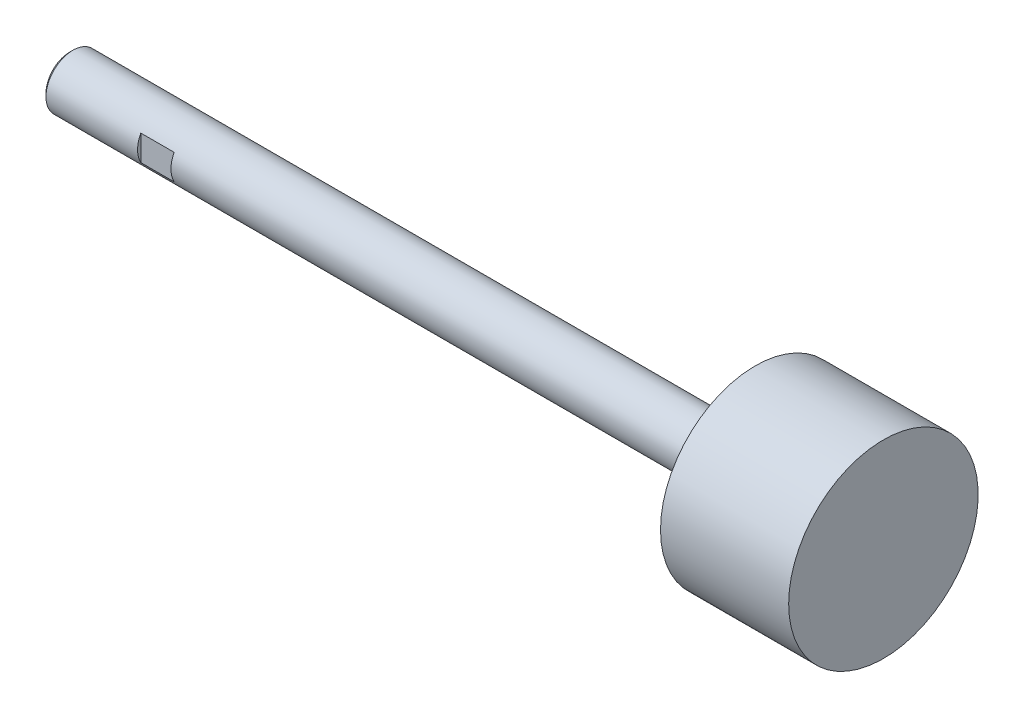
SolidWorks part; units mm, degrees
material "Cast Alloy Steel"
ref_plane "Front Plane" through (0, 0, 0) normal (0, 0, 1) x (1, 0, 0)
ref_plane "Top Plane" through (0, 0, 0) normal (0, 1, 0) x (1, 0, 0)
ref_plane "Right Plane" through (0, 0, 0) normal (1, 0, 0) x (0, 0, -1)
sketch "Sketch1" plane through (0, 0, 0) normal (0, 0, 1) x (1, 0, 0)
  line L0 (-7.874, 0) -> (-7.874, 6.35)
  line L1 (-7.874, 6.35) -> (131.445, 6.35)
  line L2 (131.445, 6.35) -> (131.445, 22.3456)
  line L3 (131.445, 22.3456) -> (161.671, 22.3456)
  line L4 (161.671, 22.3456) -> (161.671, 0)
  line L5 (161.671, 0) -> (-7.874, 0)
  line L6 (161.671, 0) -> (-7.874, 0) construction
revolve "Revolve1" add sketch "Sketch1" angle 360 about L6 reverse direction yes
cosmetic thread "Cosmetic Thread1" parameters "D1"=22.352, "D2"=11.1887
sketch "Sketch2" plane through (0, 0, 0) normal (0, 0, 1) x (1, 0, 0)
  line L0 (-30.226, 0) -> (-30.226, 5.5944)
  line L1 (-30.226, 5.5944) -> (-29.4703, 6.35)
  line L2 (-29.4703, 6.35) -> (-7.874, 6.35)
  line L3 (-7.874, 6.35) -> (-7.874, 0)
  line L4 (-7.874, 0) -> (-30.226, 0)
  line L5 (-7.874, 0) -> (-30.226, 0) construction
revolve "Revolve2" add sketch "Sketch2" angle 360 about L5 reverse direction yes
ref_plane "Plane1" through (0, 0, 0) normal (1, 0, 0) x (0, 0, -1)
ref_plane "Plane2" through (-7.874, 0, 0) normal (1, 0, 0) x (0, 0, -1)
sketch "Sketch3" plane through (-7.874, 0, 0) normal (1, 0, 0) x (0, 0, -1)
  line L0 (-12.7, 12.7) -> (-12.7, -12.7)
  line L1 (-12.7, -12.7) -> (12.7, -12.7)
  line L2 (12.7, -12.7) -> (12.7, 12.7)
  line L3 (12.7, 12.7) -> (-12.7, 12.7)
  line L4 (-5.588, 6.35) -> (-5.588, -6.35)
  line L5 (-5.588, -6.35) -> (5.588, -6.35)
  line L6 (5.588, -6.35) -> (5.588, 6.35)
  line L7 (5.588, 6.35) -> (-5.588, 6.35)
extrude "Cut-Extrude1" cut sketch "Sketch3" along normal blind 7.874
ref_plane "Plane3" through (300.99, 0, 0) normal (1, 0, 0) x (0, 0, -1)
ref_plane "Plane4" through (-30.226, 0, 0) normal (1, 0, 0) x (0, 0, -1)
ref_plane "Plane5" through (-7.874, 0, 0) normal (1, 0, 0) x (0, 0, -1)
ref_plane "Plane6" through (0, 0, 0) normal (1, 0, 0) x (0, 0, -1)
ref_plane "Plane7" through (0, 0, 0) normal (0, 0, 1) x (1, 0, 0)
ref_plane "Plane8" through (0, 0, 0) normal (1, 0, 0) x (0, 0, -1)
ref_plane "Plane9" through (0, 0, 0) normal (0, 1, 0) x (1, 0, 0)
ref_plane "Plane10" through (-34.798, 0, 0) normal (1, 0, 0) x (0, 0, -1)
ref_plane "dia1 XY" through (-7.874, 0, 0) normal (1, 0, 0) x (0, 0, -1)
ref_plane "dia1 XZ" through (0, 6.35, 0) normal (0, -1, 0) x (-1, 0, 0)
ref_plane "dia1 YZ" through (0, 0, 0) normal (0, 0, -1) x (-1, 0, 0)
ref_axis "dia1 X" through (-7.874, 6.35, 80.9) along (0, 0, -1)
ref_axis "dia1 Y" through (-7.874, -50, 0) along (0, 1, 0)
ref_axis "dia1 Z" through (80.9, 6.35, 0) along (-1, 0, 0)
sketch3d "dia1"
  point P0 (-7.874, 6.35, 0)
ref_plane "dia12 XY" through (0, 0, 0) normal (1, 0, 0) x (0, 0, -1)
ref_plane "dia12 XZ" through (0, 0, 0) normal (0, -1, 0) x (-1, 0, 0)
ref_plane "dia12 YZ" through (0, 0, 23.4251) normal (0, 0, -1) x (-1, 0, 0)
ref_axis "dia12 X" through (0, 0, 80.9) along (0, 0, -1)
ref_axis "dia12 Y" through (0, -50, 23.4251) along (0, 1, 0)
ref_axis "dia12 Z" through (80.9, 0, 23.4251) along (-1, 0, 0)
sketch3d "dia12"
  point P0 (0, 0, 23.4251)
ref_plane "dia2 XY" through (-7.874, 0, 0) normal (1, 0, 0) x (0, 0, -1)
ref_plane "dia2 XZ" through (0, -6.35, 0) normal (0, -1, 0) x (-1, 0, 0)
ref_plane "dia2 YZ" through (0, 0, 0) normal (0, 0, -1) x (-1, 0, 0)
ref_axis "dia2 X" through (-7.874, -6.35, 80.9) along (0, 0, -1)
ref_axis "dia2 Y" through (-7.874, -50, 0) along (0, 1, 0)
ref_axis "dia2 Z" through (80.9, -6.35, 0) along (-1, 0, 0)
sketch3d "dia2"
  point P0 (-7.874, -6.35, 0)
ref_plane "dia22 XY" through (0, 0, 0) normal (1, 0, 0) x (0, 0, -1)
ref_plane "dia22 XZ" through (0, 0, 0) normal (0, -1, 0) x (-1, 0, 0)
ref_plane "dia22 YZ" through (0, 0, -23.4251) normal (0, 0, -1) x (-1, 0, 0)
ref_axis "dia22 X" through (0, 0, 80.9) along (0, 0, -1)
ref_axis "dia22 Y" through (0, -50, -23.4251) along (0, 1, 0)
ref_axis "dia22 Z" through (80.9, 0, -23.4251) along (-1, 0, 0)
sketch3d "dia22"
  point P0 (0, 0, -23.4251)
ref_plane "hh1 XY" through (0, 0, 0) normal (0, 0, 1) x (1, 0, 0)
ref_plane "hh1 XZ" through (0, 0, 0) normal (0, -1, 0) x (-1, 0, 0)
ref_plane "hh1 YZ" through (204.5081, 0, 0) normal (1, 0, 0) x (0, 0, -1)
ref_axis "hh1 X" through (-80.9, 0, 0) along (1, 0, 0)
ref_axis "hh1 Y" through (204.5081, -50, 0) along (0, 1, 0)
ref_axis "hh1 Z" through (204.5081, 0, 80.9) along (0, 0, -1)
sketch3d "hh1"
  point P0 (204.5081, 0, 0)
ref_plane "hh2 XY" through (0, 0, 0) normal (0, 0, 1) x (1, 0, 0)
ref_plane "hh2 XZ" through (0, 0, 0) normal (0, -1, 0) x (-1, 0, 0)
ref_plane "hh2 YZ" through (214.0839, 0, 0) normal (1, 0, 0) x (0, 0, -1)
ref_axis "hh2 X" through (-80.9, 0, 0) along (1, 0, 0)
ref_axis "hh2 Y" through (214.0839, -50, 0) along (0, 1, 0)
ref_axis "hh2 Z" through (214.0839, 0, 80.9) along (0, 0, -1)
sketch3d "hh2"
  point P0 (214.0839, 0, 0)
ref_plane "rl1 XY" through (-30.226, 0, 0) normal (1, 0, 0) x (0, 0, -1)
ref_plane "rl1 XZ" through (0, 0, 0) normal (0, -1, 0) x (-1, 0, 0)
ref_plane "rl1 YZ" through (0, 0, 0) normal (0, 0, -1) x (-1, 0, 0)
ref_axis "rl1 X" through (-30.226, 0, 80.9) along (0, 0, -1)
ref_axis "rl1 Y" through (-30.226, -50, 0) along (0, 1, 0)
ref_axis "rl1 Z" through (80.9, 0, 0) along (-1, 0, 0)
sketch3d "rl1"
  point P0 (-30.226, 0, 0)
ref_plane "rl2 XY" through (-7.874, 0, 0) normal (1, 0, 0) x (0, 0, -1)
ref_plane "rl2 XZ" through (0, 0, 0) normal (0, -1, 0) x (-1, 0, 0)
ref_plane "rl2 YZ" through (0, 0, 0) normal (0, 0, -1) x (-1, 0, 0)
ref_axis "rl2 X" through (-7.874, 0, 80.9) along (0, 0, -1)
ref_axis "rl2 Y" through (-7.874, -50, 0) along (0, 1, 0)
ref_axis "rl2 Z" through (80.9, 0, 0) along (-1, 0, 0)
sketch3d "rl2"
  point P0 (-7.874, 0, 0)
ref_plane "rod_cp XY" through (0, 0, 0) normal (1, 0, 0) x (0, 0, -1)
ref_plane "rod_cp XZ" through (0, 0, 0) normal (0, -1, 0) x (-1, 0, 0)
ref_plane "rod_cp YZ" through (0, 0, 0) normal (0, 0, -1) x (-1, 0, 0)
ref_axis "rod_cp X" through (0, 0, 80.9) along (0, 0, -1)
ref_axis "rod_cp Y" through (0, -50, 0) along (0, 1, 0)
ref_axis "rod_cp Z" through (80.9, 0, 0) along (-1, 0, 0)
sketch3d "rod_cp"
  point P0 (0, 0, 0)
ref_plane "thd1 XY" through (-30.226, 0, 0) normal (1, 0, 0) x (0, 0, -1)
ref_plane "thd1 XZ" through (0, 6.35, 0) normal (0, -1, 0) x (-1, 0, 0)
ref_plane "thd1 YZ" through (0, 0, 0) normal (0, 0, -1) x (-1, 0, 0)
ref_axis "thd1 X" through (-30.226, 6.35, 80.9) along (0, 0, -1)
ref_axis "thd1 Y" through (-30.226, -50, 0) along (0, 1, 0)
ref_axis "thd1 Z" through (80.9, 6.35, 0) along (-1, 0, 0)
sketch3d "thd1"
  point P0 (-30.226, 6.35, 0)
ref_plane "thd2 XY" through (-30.226, 0, 0) normal (1, 0, 0) x (0, 0, -1)
ref_plane "thd2 XZ" through (0, -6.35, 0) normal (0, -1, 0) x (-1, 0, 0)
ref_plane "thd2 YZ" through (0, 0, 0) normal (0, 0, -1) x (-1, 0, 0)
ref_axis "thd2 X" through (-30.226, -6.35, 80.9) along (0, 0, -1)
ref_axis "thd2 Y" through (-30.226, -50, 0) along (0, 1, 0)
ref_axis "thd2 Z" through (80.9, -6.35, 0) along (-1, 0, 0)
sketch3d "thd2"
  point P0 (-30.226, -6.35, 0)
ref_plane "to_rod_clevis XY" through (-34.798, 0, 0) normal (1, 0, 0) x (0, 0, -1)
ref_plane "to_rod_clevis XZ" through (0, 0, 0) normal (0, -1, 0) x (-1, 0, 0)
ref_plane "to_rod_clevis YZ" through (0, 0, 0) normal (0, 0, -1) x (-1, 0, 0)
ref_axis "to_rod_clevis X" through (-34.798, 0, 80.9) along (0, 0, -1)
ref_axis "to_rod_clevis Y" through (-34.798, -50, 0) along (0, 1, 0)
ref_axis "to_rod_clevis Z" through (80.9, 0, 0) along (-1, 0, 0)
sketch3d "to_rod_clevis"
  point P0 (-34.798, 0, 0)
ref_plane "wf1 XY" through (-7.874, 0, 0) normal (1, 0, 0) x (0, 0, -1)
ref_plane "wf1 XZ" through (0, 0, 0) normal (0, -1, 0) x (-1, 0, 0)
ref_plane "wf1 YZ" through (0, 0, 0) normal (0, 0, -1) x (-1, 0, 0)
ref_axis "wf1 X" through (-7.874, 0, 80.9) along (0, 0, -1)
ref_axis "wf1 Y" through (-7.874, -50, 0) along (0, 1, 0)
ref_axis "wf1 Z" through (80.9, 0, 0) along (-1, 0, 0)
sketch3d "wf1"
  point P0 (-7.874, 0, 0)
ref_plane "wf2 XY" through (0, 0, 0) normal (1, 0, 0) x (0, 0, -1)
ref_plane "wf2 XZ" through (0, 0, 0) normal (0, -1, 0) x (-1, 0, 0)
ref_plane "wf2 YZ" through (0, 0, 0) normal (0, 0, -1) x (-1, 0, 0)
ref_axis "wf2 X" through (0, 0, 80.9) along (0, 0, -1)
ref_axis "wf2 Y" through (0, -50, 0) along (0, 1, 0)
ref_axis "wf2 Z" through (80.9, 0, 0) along (-1, 0, 0)
sketch3d "wf2"
  point P0 (0, 0, 0)
ref_plane "wfw1 XY" through (0, 0, 0) normal (0, 1, 0) x (1, 0, 0)
ref_plane "wfw1 XZ" through (0, 0, -5.588) normal (0, 0, 1) x (1, 0, 0)
ref_plane "wfw1 YZ" through (-7.874, 0, 0) normal (1, 0, 0) x (0, 0, -1)
ref_axis "wfw1 X" through (-80.9, 0, -5.588) along (1, 0, 0)
ref_axis "wfw1 Y" through (-7.874, 0, 50) along (0, 0, -1)
ref_axis "wfw1 Z" through (-7.874, 50, -5.588) along (0, -1, 0)
sketch3d "wfw1"
  point P0 (-7.874, 0, -5.588)
ref_plane "wfw2 XY" through (0, 0, 0) normal (0, 1, 0) x (1, 0, 0)
ref_plane "wfw2 XZ" through (0, 0, 5.588) normal (0, 0, 1) x (1, 0, 0)
ref_plane "wfw2 YZ" through (-7.874, 0, 0) normal (1, 0, 0) x (0, 0, -1)
ref_axis "wfw2 X" through (-80.9, 0, 5.588) along (1, 0, 0)
ref_axis "wfw2 Y" through (-7.874, 0, 50) along (0, 0, -1)
ref_axis "wfw2 Z" through (-7.874, 50, 5.588) along (0, -1, 0)
sketch3d "wfw2"
  point P0 (-7.874, 0, 5.588)
